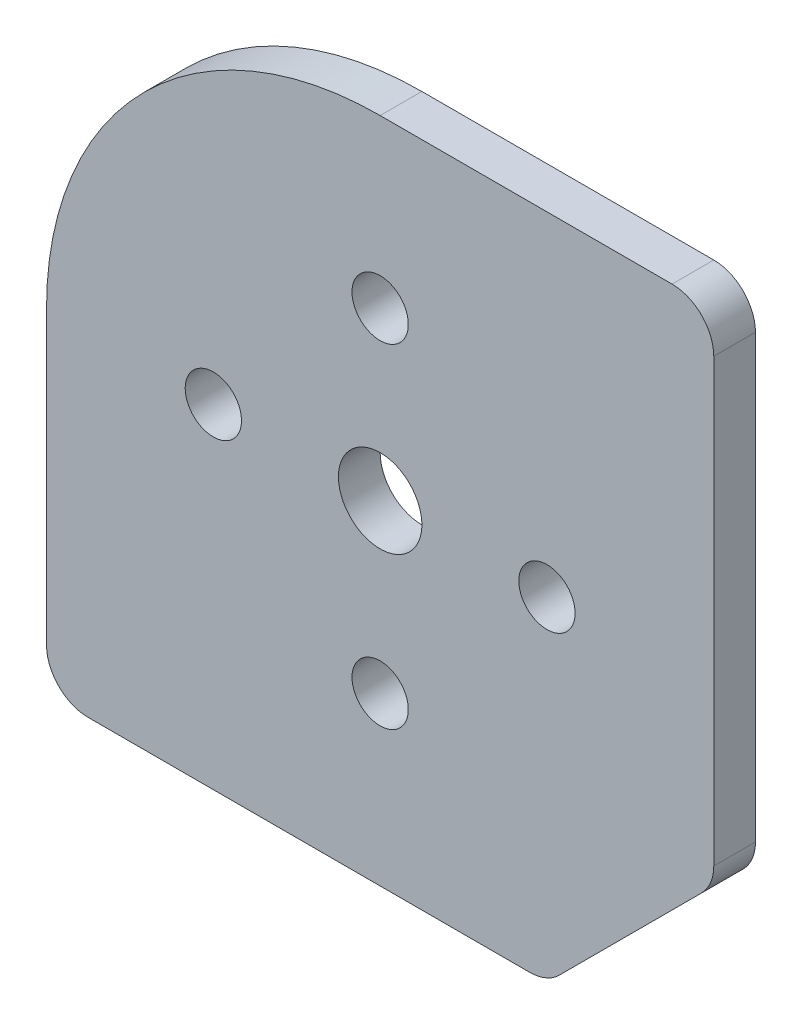
SolidWorks part; units mm, degrees
ref_plane "Front Plane" through (0, 0, 0) normal (0, 0, 1) x (1, 0, 0)
ref_plane "Top Plane" through (0, 0, 0) normal (0, 1, 0) x (1, 0, 0)
ref_plane "Right Plane" through (0, 0, 0) normal (1, 0, 0) x (0, 0, -1)
sketch "Sketch1" plane through (0, 0, 0) normal (0, 0, 1) x (1, 0, 0)
  line L0 (-350, 180) -> (-350, 270) construction
  line L1 (-320, 220) -> (-220, 220) construction
  line L2 (-320, 220) -> (-320, 320) construction
  line L3 (-320, 320) -> (-220, 320) construction
  line L4 (-220, 220) -> (-220, 320) construction
  line L5 (-320, 220) -> (-220, 320) construction
  line L6 (-320, 320) -> (-220, 220) construction
  line L11 (-270, 350) -> (-180, 350) construction
  line L12 (-350, 190) -> (-350, 270)
  line L13 (-270, 350) -> (-190, 350)
  line L14 (-350, 190) -> (-230, 190)
  line L15 (-190, 230) -> (-190, 350)
  line L16 (-230, 190) -> (-190, 230)
  arc A0 (-270, 350) -> (-350, 270) centre (-270, 270) ccw construction
  arc A1 (-270, 350) -> (-350, 270) centre (-270, 270) ccw
  point P0 (-270, 270)
  point P6 (-270, 270)
  point P12 (-190, 190)
  dimension "D1" = 100
  dimension "D2" = 100
  dimension "D3" = 30
  dimension "D4" = 30
base flange "Base-Flange1" sketch "Sketch1" thickness 10 reverse thickness direction yes parameters "D1"=5
sketch "Sketch6" plane through (0, 0, 0) normal (0, 0, -1) x (-1, 0, 0)
  circle A0 centre (270, 310) radius 6.75
  circle A1 centre (310, 270) radius 6.75
  circle A2 centre (230, 270) radius 6.75
  circle A3 centre (270, 230) radius 6.75
  circle A4 centre (270, 270) radius 10
  dimension "D1" = 13.5
  dimension "D2" = 20
extrude "Cut-Extrude1" cut sketch "Sketch6" against normal through all normal cut yes
fillet "Fillet1" radius 10 4 edges at (-350, 190, 5) (-230, 190, 5) (-190, 230, 5) (-190, 350, 5)
sketch "Bend-Lines1" [suppressed] plane through (0, 0, 0) normal (0, 1, 0) x (1, 0, 0)
sketch "Bounding-Box1" [suppressed] plane through (0, 0, 0) normal (0, 1, 0) x (1, 0, 0)
sheet metal parameters "Sheet-Metal1" thickness 10 parameters "D1"=5
flat pattern "Flat-Pattern1" [suppressed]
sketch "Bend-Lines2" plane through (0, 0, 0) normal (0, 1, 0) x (1, 0, 0)
sketch3d "Bounding-Box2" [suppressed]
  line L0 (-80, 80, 0) -> (-80, -80, 0) construction
  line L1 (80, 80, 0) -> (80, -80, 0) construction
  line L2 (-80, 80, 0) -> (80, 80, 0) construction
  line L3 (-80, -80, 0) -> (80, -80, 0) construction
sheet metal parameters "Sheet-Metal2" thickness 10 parameters "D1"=5
flat pattern "Flat-Pattern1"
sketch "Bend-Lines2" plane through (0, 0, 0) normal (0, 1, 0) x (1, 0, 0)
sketch3d "Bounding-Box2" [suppressed]
  line L0 (-80, 80, 0) -> (-80, -80, 0) construction
  line L1 (80, 80, 0) -> (80, -80, 0) construction
  line L2 (-80, 80, 0) -> (80, 80, 0) construction
  line L3 (-80, -80, 0) -> (80, -80, 0) construction
